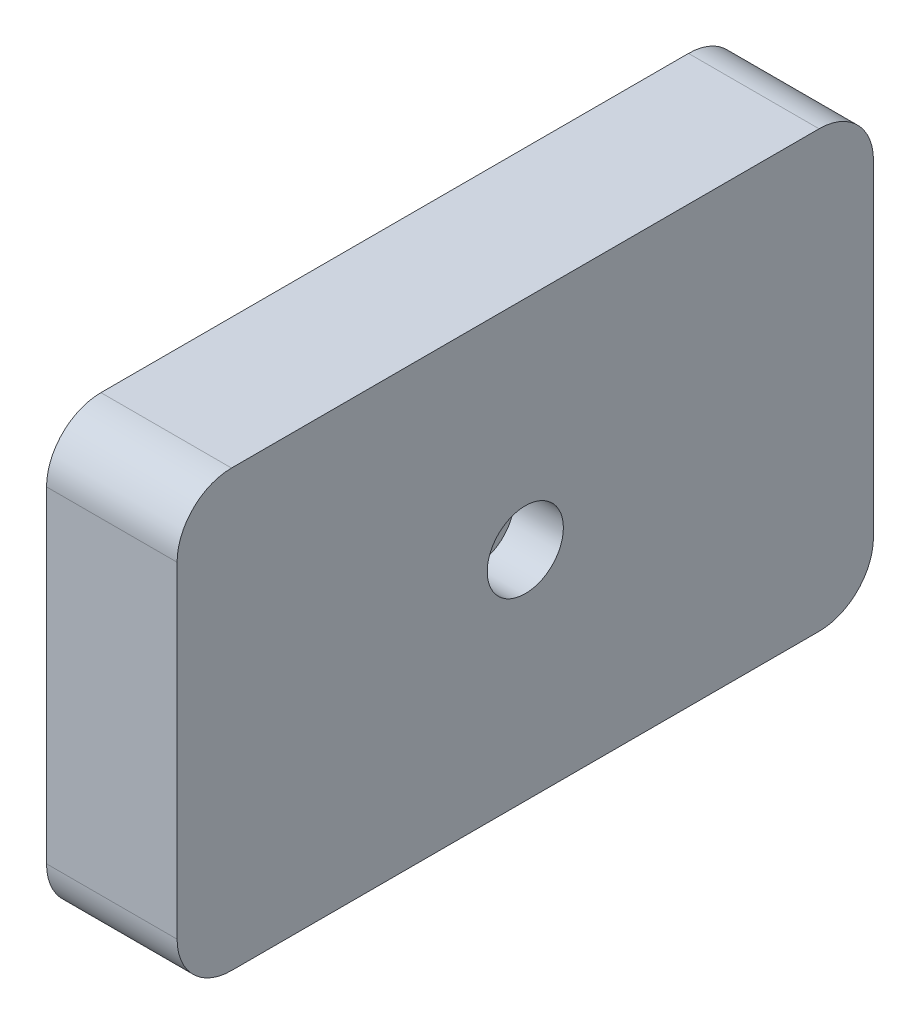
SolidWorks part; units mm, degrees
material "普通碳钢"
ref_plane "前视基准面" through (0, 0, 0) normal (0, 0, 1) x (1, 0, 0)
ref_plane "上视基准面" through (0, 0, 0) normal (0, 1, 0) x (1, 0, 0)
ref_plane "右视基准面" through (0, 0, 0) normal (1, 0, 0) x (0, 0, -1)
sketch "草图1" plane through (0, 0, 0) normal (1, 0, 0) x (0, 0, -1)
  line L1 (-27, 20) -> (27, 20)
  line L2 (-32, 15) -> (-32, -15)
  line L3 (-27, -20) -> (27, -20)
  line L4 (32, 15) -> (32, -15)
  line L5 (-32, 20) -> (32, -20) construction
  line L6 (-32, -20) -> (32, 20) construction
  arc A0 (27, 20) -> (32, 15) centre (27, 15) cw
  arc A1 (27, -20) -> (32, -15) centre (27, -15) ccw
  arc A2 (-27, -20) -> (-32, -15) centre (-27, -15) cw
  arc A3 (-32, 15) -> (-27, 20) centre (-27, 15) cw
  point P0 (0, 0)
  dimension "D3" = 5
  dimension "D1" = 64
  dimension "D2" = 40
extrude "凸台-拉伸1" add sketch "草图1" along normal blind 12
sketch "草图2" plane through (0, 0, 0) normal (-1, 0, 0) x (0, 0, 1)
  circle A1 centre (0, 0) radius 8
  dimension "D1" = 16
extrude "切除-拉伸1" cut sketch "草图2" against normal blind 5 contours A1
sketch "草图4" plane through (12, 0, 0) normal (1, 0, 0) x (0, 0, -1)
  circle A1 centre (0, 0) radius 8
  circle A2 centre (0, 0) radius 8 construction
  dimension "D1" = 0
hole_wizard "孔1" positions "3D草图1" profile "草图5" legacy
sketch3d "3D草图1"
  point P0 (0, 0, 0)
  point P3 (12, 0, 0)
  point P6 (0, 0, 0)
sketch "草图5" plane through (12, 0, 0) normal (0, 1, 0) x (0, 0, -1)
  line L0 (0, 0) -> (0, 12)
  line L1 (0, 12) -> (2, 12)
  line L3 (2, 12) -> (2, 4.5)
  line L4 (2, 4.5) -> (3.5, 4.5)
  line L5 (3.5, 4.5) -> (3.5, 0)
  line L7 (3.5, 0) -> (0, 0)
  line L11 (0, -6.35) -> (0, 107.95) construction
  dimension "通孔孔直径" = 4
  dimension "通孔孔深度" = 12
  dimension "柱形沉头孔直径" = 7
  dimension "柱形沉头孔深度" = 4.5
